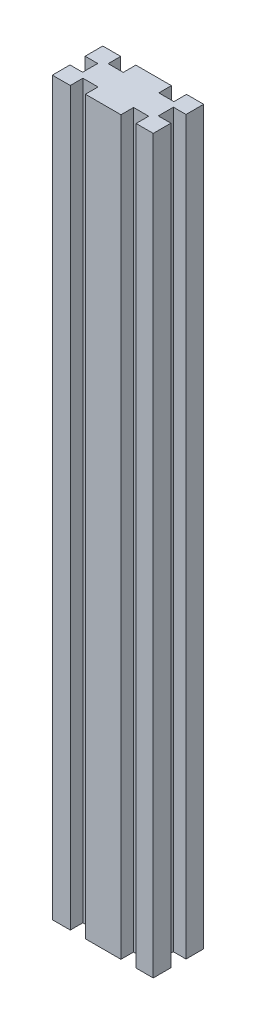
SolidWorks part; units mm, degrees
ref_plane "Спереди" through (0, 0, 0) normal (0, 0, 1) x (1, 0, 0)
ref_plane "Сверху" through (0, 0, 0) normal (0, 1, 0) x (1, 0, 0)
ref_plane "Справа" through (0, 0, 0) normal (1, 0, 0) x (0, 0, -1)
sketch "Эскиз1" plane through (0, 0, 0) normal (0, 1, 0) x (1, 0, 0)
  line L0 (5, 10) -> (35, 10) construction
  line L1 (0, 0) -> (7.1145, 0)
  line L2 (0, 20) -> (0, 13)
  line L3 (0, 20) -> (7.1145, 20)
  line L4 (40, 20) -> (40, 13)
  line L5 (30.2024, 15) -> (30.2024, 5) construction
  line L6 (10.1145, 15) -> (10.1145, 5) construction
  line L7 (20, 20) -> (20, 0) construction
  line L8 (7.1145, 20) -> (7.1145, 15)
  line L9 (7.1145, 15) -> (13.1145, 15)
  line L10 (13.1145, 15) -> (13.1145, 20)
  line L11 (13.1145, 20) -> (27.2024, 20)
  line L12 (27.2024, 20) -> (27.2024, 15)
  line L13 (27.2024, 15) -> (33.2024, 15)
  line L14 (33.2024, 15) -> (33.2024, 20)
  line L15 (33.2024, 20) -> (40, 20)
  line L16 (7.1145, 0) -> (7.1145, 5)
  line L17 (7.1145, 5) -> (13.1145, 5)
  line L18 (13.1145, 5) -> (13.1145, 0)
  line L19 (13.1145, 0) -> (27.2024, 0)
  line L20 (27.2024, 0) -> (27.2024, 5)
  line L21 (27.2024, 5) -> (33.2024, 5)
  line L22 (33.2024, 5) -> (33.2024, 0)
  line L23 (33.2024, 0) -> (40, 0)
  line L24 (40, 13) -> (35, 13)
  line L25 (35, 13) -> (35, 7)
  line L26 (35, 7) -> (40, 7)
  line L27 (40, 7) -> (40, 0)
  line L28 (0, 13) -> (5, 13)
  line L29 (5, 13) -> (5, 7)
  line L30 (5, 7) -> (0, 7)
  line L31 (0, 7) -> (0, 0)
  dimension "D1" = 6
  dimension "D2" = 6
  dimension "D3" = 6
  dimension "D4" = 6
  dimension "D5" = 5
  dimension "D6" = 6
  dimension "D7" = 6
  dimension "D8" = 40
  dimension "D9" = 20
  dimension "D10" = 5
extrude "Бобышка-Вытянуть1" add sketch "Эскиз1" along normal blind 290
